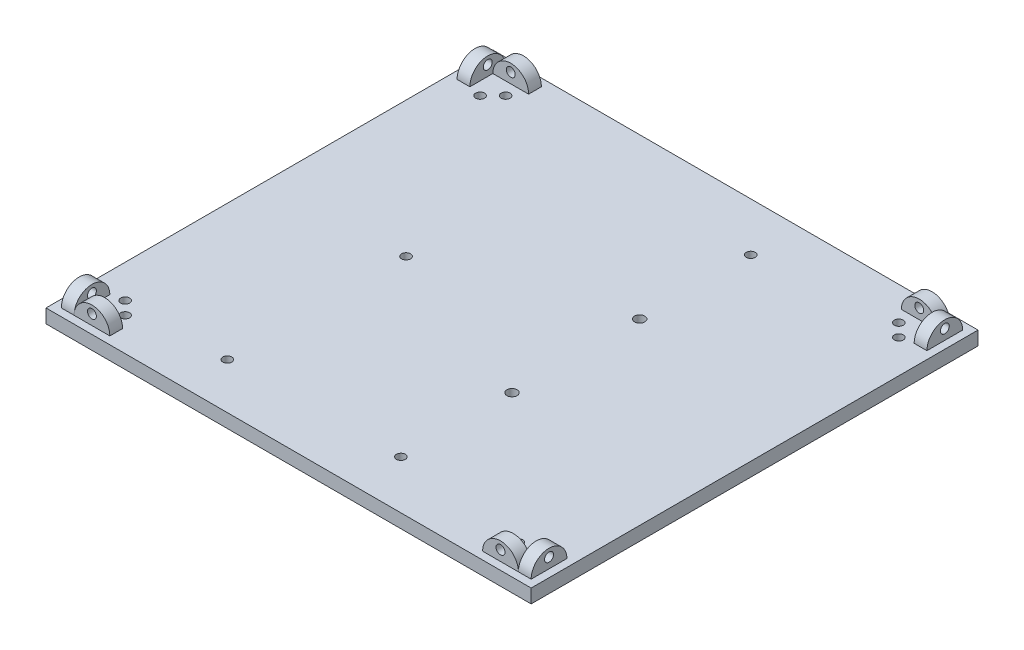
SolidWorks part; units mm, degrees
ref_plane "Front Plane" through (0, 0, 0) normal (0, 0, 1) x (1, 0, 0)
ref_plane "Top Plane" through (0, 0, 0) normal (0, 1, 0) x (1, 0, 0)
ref_plane "Right Plane" through (0, 0, 0) normal (1, 0, 0) x (0, 0, -1)
sketch "Sketch1" plane through (0, 0, 0) normal (0, 1, 0) x (1, 0, 0)
  line L1 (-26.0644, -19.3857) -> (126.4356, -19.3857) construction
  line L2 (-26.0644, -19.3857) -> (-26.0644, 30.6143) construction
  line L3 (-26.0644, 30.6143) -> (126.4356, 30.6143) construction
  line L4 (126.4356, -19.3857) -> (126.4356, 30.6143) construction
  line L5 (-143.0644, 90.1143) -> (40.9356, 90.1143) construction
  line L6 (40.9356, -78.8857) -> (40.9356, 90.1143) construction
  line L10 (-146.0644, 93.1143) -> (43.9356, 93.1143)
  line L11 (43.9356, -81.8857) -> (43.9356, 93.1143)
  line L12 (-146.0644, -81.8857) -> (43.9356, -81.8857)
  line L13 (-146.0644, -81.8857) -> (-146.0644, 93.1143)
  line L14 (-143.0644, -78.8857) -> (40.9356, -78.8857) construction
  line L15 (-143.0644, -78.8857) -> (-143.0644, 90.1143) construction
  line L17 (113.9356, 62.2405) -> (53.9356, 62.2405) construction
  line L18 (113.9356, 62.2405) -> (113.9356, 2.2405) construction
  line L19 (113.9356, 2.2405) -> (53.9356, 2.2405) construction
  line L20 (53.9356, 62.2405) -> (53.9356, 2.2405) construction
  line L21 (-51.0644, 90.1143) -> (-51.0644, -78.8857) construction
  line L22 (-143.0644, 5.6143) -> (40.9356, 5.6143) construction
  line L23 (-26.0644, -19.3857) -> (-26.0644, -67.8857) construction
  line L24 (-26.0644, -67.8857) -> (-26.0644, -62.8857) construction
  line L25 (-26.0644, 30.6143) -> (-26.0644, 79.1143) construction
  line L26 (-26.0644, 79.1143) -> (-26.0644, 74.1143) construction
  line L27 (-93.0644, 11.1143) -> (-93.0644, -68.8857) construction
  line L28 (-118.0644, 11.1143) -> (-68.0644, 11.1143) construction
  line L29 (-118.0644, 11.1143) -> (-118.0644, -68.8857) construction
  line L30 (-118.0644, -68.8857) -> (-68.0644, -68.8857) construction
  line L31 (-68.0644, 11.1143) -> (-68.0644, -68.8857) construction
  line L32 (-118.0644, 11.1143) -> (-68.0644, -68.8857) construction
  line L33 (-118.0644, -68.8857) -> (-68.0644, 11.1143) construction
  line L34 (-93.0644, 11.1143) -> (-93.0644, 6.1143) construction
  line L35 (-93.0644, -68.8857) -> (-93.0644, -63.8857) construction
  circle A0 centre (-26.0644, 30.6143) radius 2
  circle A1 centre (-26.0644, -19.3857) radius 2
  circle A2 centre (-26.0644, -62.8857) radius 1.75
  circle A3 centre (-26.0644, 74.1143) radius 1.75
  circle A4 centre (-93.0644, 6.1143) radius 1.75
  circle A5 centre (-93.0644, -63.8857) radius 1.75
  point P29 (-93.0644, -28.8857)
  dimension "D6" = 4
  dimension "D14" = 3.5
  dimension "D15" = 5
  dimension "D17" = 3.5
  dimension "D22" = 3.5
  dimension "D23" = 3.5
  dimension "D1" = 50
  dimension "D2" = 80
  dimension "D4" = 200
  dimension "D5" = 59.5
  dimension "D9" = 175
  dimension "D10" = 190
  dimension "D11" = 60
  dimension "D12" = 70
  dimension "D13" = 48.5
  dimension "D3" = 3
  dimension "D8" = 5
  dimension "D16" = 48.5
  dimension "D18" = 50
  dimension "D19" = 25
  dimension "D20" = 10
  dimension "D21" = 5
  dimension "D7" = 2
extrude "Base" add sketch "Sketch1" against normal blind 5.4
ref_plane "Plane1" through (-143.0644, 0, 0) normal (1, 0, 0) x (0, 0, -1)
sketch "Sketch3" plane through (-143.0644, 0, 0) normal (1, 0, 0) x (0, 0, -1)
  line L1 (-78.8857, 0) -> (90.1143, 0) construction
  line L2 (90.1143, 0) -> (83.1143, 0) construction
  line L3 (76.1143, 0) -> (90.1143, 0)
  line L4 (-78.8857, 0) -> (-64.8857, 0)
  line L5 (-71.8857, 7) -> (-71.8857, 0) construction
  line L6 (83.1143, 7) -> (83.1143, 0) construction
  line L7 (-78.8857, 0) -> (90.1143, 0) construction
  arc A0 (90.1143, 0) -> (76.1143, 0) centre (83.1143, 0) ccw
  arc A1 (-64.8857, 0) -> (-78.8857, 0) centre (-71.8857, 0) ccw
  circle A2 centre (-71.8857, 4) radius 1.75
  circle A3 centre (83.1143, 4) radius 1.75
  point P18 (93.1143, 0)
  dimension "D1" = 14
  dimension "D2" = 3.5
  dimension "D4" = 3.5
  dimension "D3" = 3
  dimension "D5" = 4
  dimension "D6" = 14
extrude "Long_Side_connectors" add sketch "Sketch3" along normal blind 5
ref_plane "Plane2" through (0, 0, 78.8857) normal (0, 0, 1) x (1, 0, 0)
sketch "Sketch4" plane through (0, 0, 78.8857) normal (0, 0, 1) x (1, 0, 0)
  line L1 (-138.0644, 0) -> (-124.0644, 0)
  line L2 (-138.0644, 0) -> (-124.0644, 0)
  line L3 (-131.0644, 7) -> (-131.0644, 0) construction
  arc A0 (-124.0644, 0) -> (-138.0644, 0) centre (-131.0644, 0) ccw
  circle A1 centre (-131.0644, 4) radius 1.75
  dimension "D1" = 14
  dimension "D2" = 4
extrude "Short_side_connectors" add sketch "Sketch4" against normal blind 5 contours A0 L3 A1 L2 | L3 A0 L1 A1 region at (-134.3536, 2.8239, 78.8857) region at (-127.7752, 2.8239, 78.8857)
ref_plane "Plane6" through (0, 0, -5.6143) normal (0, 0, 1) x (1, 0, 0)
mirror "Mirror1" about plane through (0, 0, -5.6143) normal (0, 0, 1) of "Short_side_connectors"
ref_plane "Plane5" through (-51.0644, 0, 0) normal (1, 0, 0) x (0, 0, -1)
mirror "Mirror3" about plane through (-51.0644, 0, 0) normal (1, 0, 0) of "Long_Side_connectors", "Mirror1"
sketch "Sketch6" plane through (0, 0, 0) normal (0, 1, 0) x (1, 0, 0)
  line L0 (126.4356, -19.3857) -> (126.4356, 30.6143) construction
  line L1 (136.4356, -62.7595) -> (216.4356, -62.7595)
  line L2 (136.4356, -62.7595) -> (136.4356, -12.7595)
  line L3 (136.4356, -12.7595) -> (216.4356, -12.7595)
  line L4 (216.4356, -62.7595) -> (216.4356, -12.7595)
  line L5 (136.4356, -62.7595) -> (216.4356, -12.7595) construction
  line L6 (136.4356, -12.7595) -> (216.4356, -62.7595) construction
  line L7 (113.9356, 2.2405) -> (53.9356, 2.2405) construction
  point P0 (176.4356, -37.7595)
  point P9 (83.9356, 2.2405)
  dimension "D1" = 50
  dimension "D2" = 80
  dimension "D3" = 10
  dimension "D4" = 15
extrude "Estop_relay" [suppressed] add sketch "Sketch6" along normal blind 2 contours L3 L4 L1 L2
sketch "Sketch8" [suppressed] plane through (0, 2, 0) normal (0, 1, 0) x (1, 0, 0)
  line L0 (38.9356, -37.7595) -> (118.9356, -37.7595) construction
  line L1 (38.9356, -62.7595) -> (38.9356, -12.7595) construction
  line L2 (118.9356, -62.7595) -> (118.9356, -12.7595) construction
  line L3 (38.9356, -37.7595) -> (43.9356, -37.7595) construction
  line L4 (78.9356, -12.7595) -> (78.9356, -62.7595) construction
  line L5 (38.9356, -12.7595) -> (118.9356, -12.7595) construction
  line L6 (38.9356, -62.7595) -> (118.9356, -62.7595) construction
  circle A0 centre (43.9356, -37.7595) radius 1.77
  circle A1 centre (113.9356, -37.7595) radius 1.77
  dimension "D2" = 3.54
  dimension "D1" = 5
extrude "Estop_bolts" [suppressed] cut sketch "Sketch8" against normal blind 5.3
sketch "Sketch9" plane through (0, 0, 0) normal (0, 1, 0) x (1, 0, 0)
  line L0 (-128.0644, 30.1143) -> (-128.0644, 5.1143) construction
  line L1 (-120.5644, 30.1143) -> (-120.5644, 5.1143)
  line L2 (-135.5644, 30.1143) -> (-135.5644, 5.1143)
  line L3 (-143.0644, 90.1143) -> (40.9356, 90.1143) construction
  line L4 (-143.0644, -78.8857) -> (-143.0644, 90.1143) construction
  arc A0 (-120.5644, 30.1143) -> (-135.5644, 30.1143) centre (-128.0644, 30.1143) ccw
  arc A1 (-135.5644, 5.1143) -> (-120.5644, 5.1143) centre (-128.0644, 5.1143) ccw
  point P2 (-128.0644, 17.6143)
  dimension "D1" = 25
  dimension "D2" = 15
  dimension "D3" = 60
  dimension "D4" = 15
extrude "Cut-Extrude4" [suppressed] cut sketch "Sketch9" against normal up to next contours A0 L2 A1 L1
sketch "Sketch10" [suppressed] plane through (0, 0, 0) normal (0, 1, 0) x (1, 0, 0)
  line L0 (-126.8751, 25.1928) -> (-127.2079, -70.1564) construction
  line L1 (-120.5644, 30.1143) -> (-120.5644, 5.1143) construction
  text T0 "Power"
  text T1 "  M-     M+    B-    B+    Bd   - Bd+  Bed_out+   -\r\n"
  dimension "D1" = 0.2
extrude "Text" [suppressed] cut sketch "Sketch10" against normal blind 1 and the other way through all
sketch "Sketch11" plane through (0, 0, 0) normal (0, 1, 0) x (1, 0, 0)
  line L0 (-138.0644, -73.8857) -> (-124.0644, -73.8857) construction
  line L1 (-133.0644, -68.8857) -> (-128.0644, -68.8857) construction
  line L2 (-133.0644, -68.8857) -> (-133.0644, -63.8857) construction
  line L3 (-133.0644, -63.8857) -> (-128.0644, -63.8857) construction
  line L4 (-128.0644, -68.8857) -> (-128.0644, -63.8857) construction
  line L5 (-138.0644, -73.8857) -> (-138.0644, -64.8857) construction
  line L6 (-138.0644, 85.1143) -> (-124.0644, 85.1143) construction
  line L7 (-133.0644, 80.1143) -> (-128.0644, 80.1143) construction
  line L8 (-133.0644, 80.1143) -> (-133.0644, 75.1143) construction
  line L9 (-133.0644, 75.1143) -> (-128.0644, 75.1143) construction
  line L10 (-128.0644, 80.1143) -> (-128.0644, 75.1143) construction
  line L11 (-138.0644, 76.1143) -> (-138.0644, 85.1143) construction
  line L12 (-51.0644, -85.25) -> (-51.0644, 85.25) construction
  circle A0 centre (-133.0644, -63.8857) radius 1.75
  circle A1 centre (-128.0644, -68.8857) radius 1.75
  circle A2 centre (-133.0644, 75.1143) radius 1.75
  circle A3 centre (-128.0644, 80.1143) radius 1.75
  circle A4 centre (30.9356, -63.8857) radius 1.75
  circle A5 centre (25.9356, -68.8857) radius 1.75
  circle A6 centre (30.9356, 75.1143) radius 1.75
  circle A7 centre (25.9356, 80.1143) radius 1.75
  dimension "D3" = 3.5
  dimension "D4" = 3.5
  dimension "D8" = 5
  dimension "D1" = 5
  dimension "D2" = 5
  dimension "D5" = 5
  dimension "D6" = 5
  dimension "4" = 5
  dimension "D7" = 5
  dimension "D9" = 5
extrude "Cut-Extrude6" cut sketch "Sketch11" along normal through all from surface starting at face at (-93.0644, -5.4, 65.6357)
